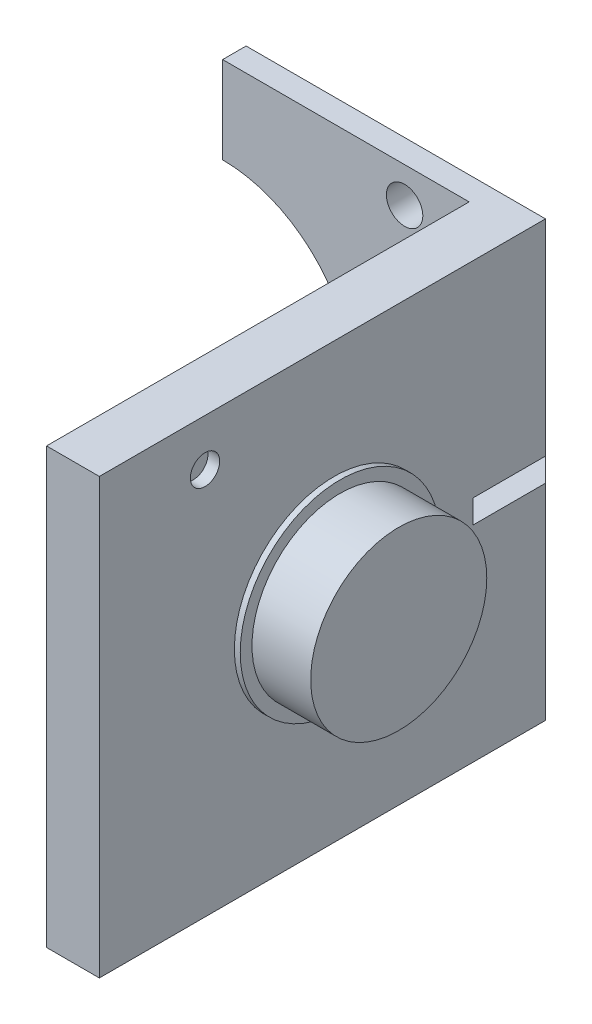
SolidWorks part; units mm, degrees
note: '?' marks a value the reader was unsure of.
ref_plane "Front Plane" through (0, 0, 0) normal (0, 0, 1) x (1, 0, 0)
ref_plane "Top Plane" through (0, 0, 0) normal (0, 1, 0) x (1, 0, 0)
ref_plane "Right Plane" through (0, 0, 0) normal (1, 0, 0) x (0, 0, -1)
sketch "Sketch1" plane through (0, 0, 0) normal (1, 0, 0) x (0, 0, -1)
  line L1 (0, 0) -> (30, 0)
  line L2 (0, 0) -> (0, 37)
  line L3 (0, 37) -> (30, 37)
  line L4 (30, 0) -> (30, 37)
  point P7 (30, 0)
  dimension "D1" = 37
  dimension "D2" = 30
extrude "Boss-Extrude1" add sketch "Sketch1" along normal blind 4.5
sketch "Sketch2" plane through (0, 0, 0) normal (-1, 0, 0) x (0, 0, 1)
  line L0 (0, 0) -> (-30, 0) construction
  line L9 (-30, 37) -> (-26, 37)
  line L10 (-30, 37) -> (-30, 0)
  line L11 (-30, 0) -> (-26, 0)
  line L12 (-26, 37) -> (-26, 0)
  dimension "D1" = 4
extrude "Boss-Extrude2" add sketch "Sketch2" along normal blind 42
sketch "Sketch3" plane through (-42, 0, 0) normal (-1, 0, 0) x (0, 0, 1)
  line L0 (-30, 37) -> (-30, 0)
  line L5 (-30, 0) -> (0, 0)
  line L6 (0, 0) -> (0, 37)
  line L7 (0, 37) -> (-30, 37)
  line L8 (-30, 37) -> (-30, 0) construction
extrude "Boss-Extrude3" add sketch "Sketch3" along normal blind 4.5
sketch "Sketch8" plane through (0, 0, -26) normal (0, 0, 1) x (1, 0, 0)
  line L0 (-42, 37) -> (0, 37) construction
  line L1 (0, 0) -> (0, 37) construction
  line L2 (-46.5, 37) -> (4.5, 0) construction
  circle A0 centre (-21, 18.5) radius 11.1
  point P5 (-21, 37)
  point P9 (0, 18.5)
  dimension "D1" = 22.2
extrude "Cut-Extrude1" cut sketch "Sketch8" against normal up to surface (4 mm away) up to face at (-21, 18.5, -30)
ref_axis "Axis1" through (-21, 18.5, -38.061) along (0, 0, 1)?
sketch "Sketch9" plane through (0, 0, -30) normal (0, 0, -1) x (-1, 0, 0)
  line L0 (5.5, 3) -> (36.5, 34) construction
  circle A0 centre (5.5, 34) radius 1.55
  circle A1 centre (36.5, 34) radius 1.55
  circle A2 centre (36.5, 3) radius 1.55
  circle A3 centre (5.5, 3) radius 1.55
  point P8 (21, 18.5)
  dimension "D4" = 3.1
  dimension "D2" = 31
  dimension "D3" = 31
extrude "Cut-Extrude2" cut sketch "Sketch9" against normal up to surface (4 mm away) up to face at (-9.9, 18.5, -26)
chamfer "Chamfer3" distance 2 angle 45 4 edges at (-21, 0, -30) (4.5, 18.5, -30) (-21, 37, -30) (-46.5, 18.5, -30)
sketch "草图6" plane through (4.5, 0, 0) normal (1, 0, 0) x (0, 0, -1)
  line L0 (38.061, 18.5) -> (-2.722, 18.5) construction
  circle A0 centre (10, 18.5) radius 7.5
  dimension "D1" = 15
extrude "凸台-拉伸2" add sketch "草图6" along normal blind 5.5
sketch "草图3" plane through (0, 37, 0) normal (0, 1, 0) x (1, 0, 0)
  circle A0 centre (4.5, 10) radius 1
sketch "草图5" plane through (-46.5, 0, 0) normal (-1, 0, 0) x (0, 0, 1)
  line L4 (-5, 18.5) -> (-15, 18.5) construction
  line L5 (-38.061, 18.5) -> (2.722, 18.5) construction
  circle A1 centre (-10, 18.5) radius 4
  point P8 (-10, 18.5)
  dimension "D1" = 8
extrude "凸台-拉伸1" add sketch "草图5" along normal blind 20.5
sketch "草图13" plane through (0, 0, 0) normal (-1, 0, 0) x (0, 0, 1)
  line L1 (-5, 22.5) -> (-5, 27)
  line L2 (-5, 27) -> (-15.5, 27)
  line L3 (-15.5, 27) -> (-15.5, 22.5)
  line L4 (-15.5, 22.5) -> (-5, 22.5)
  dimension "D1" = 4.5
sketch "草图15" plane through (-46.5, 0, 0) normal (-1, 0, 0) x (0, 0, 1)
  line L0 (-38.061, 18.5) -> (2.722, 18.5) construction
  circle A0 centre (-10, 18.5) radius 8.5
  dimension "D1" = 17
extrude "凸台-拉伸6" add sketch "草图15" along normal blind 0.5
sketch "草图16" plane through (4.5, 0, 0) normal (1, 0, 0) x (0, 0, -1)
  line L0 (38.061, 18.5) -> (-2.722, 18.5) construction
  circle A0 centre (10, 18.5) radius 8.5
  circle A1 centre (10, 18.5) radius 7.45
  dimension "D1" = 17
extrude "凸台-拉伸7" add sketch "草图16" along normal blind 0.5
sketch "草图17" plane through (0, 0, 0) normal (0, 0, 1) x (1, 0, 0)
  line L0 (0, 37) -> (4.5, 37)
  line L1 (4.5, 37) -> (4.5, 0)
  line L2 (4.5, 0) -> (0, 0)
  line L3 (0, 0) -> (0, 37)
extrude "凸台-拉伸8" add sketch "草图17" along normal blind 10
sketch "草图18" plane through (0, 37, 0) normal (0, 1, 0) x (1, 0, 0)
  line L0 (0, -8) -> (0, 2)
  line L1 (0, 26) -> (0, -10) construction
  line L2 (0, 2) -> (4.5, 2)
  line L3 (4.5, 28) -> (4.5, -10) construction
  line L4 (4.5, 2) -> (4.5, -8)
  line L5 (4.5, -8) -> (0, -8)
  line L6 (4.5, 28) -> (-46.5, 28) construction
  dimension "D1" = 10
  dimension "D2" = 26
sketch "草图23" plane through (4.5, 0, 0) normal (1, 0, 0) x (0, 0, -1)
  line L0 (-1, 42) -> (-1, 33) construction
  circle A0 centre (-1, 33) radius 1.25
  circle A1 centre (-1, 33) radius 1.25 construction
  dimension "D2" = 2.5
extrude "切除-拉伸4" cut sketch "草图23" against normal blind 1
ref_plane "基准面1" through (-21, 0, 0) normal (-1, 0, 0) x (0, 0, 1)
ref_axis "基准轴1" through (-67, 18.5, -10) along (1, 0, 0)?
sketch "草图26" plane through (-67, 0, 0) normal (-1, 0, 0) x (0, 0, 1)
  line L0 (-15, 18.5) -> (-5, 18.5) construction
  line L2 (-10, 23.5) -> (-10, 13.5) construction
  circle A0 centre (-10, 18.5) radius 5 construction
  arc A1 (-11.9365, 22) -> (-8.0635, 22) centre (-10, 21.5) cw
  arc A3 (-6.5, 20.4365) -> (-6.5, 16.5635) centre (-7, 18.5) cw
  circle A4 centre (-10, 18.5) radius 4 construction
  arc A5 (-11.9365, 15) -> (-8.0635, 15) centre (-10, 15.5) ccw
  arc A6 (-13.5, 16.5635) -> (-13.5, 20.4365) centre (-13, 18.5) cw
  circle A7 centre (-10, 18.5) radius 4
  point P5 (-10, 23.5)
  point P14 (-5, 18.5)
  point P20 (-10, 13.5)
  point P24 (-15, 18.5)
  dimension "D1" = 10
  dimension "D2" = 2
  dimension "D3" = 8
extrude "凸台-拉伸11" add sketch "草图26" against normal blind 20.5
sketch "草图25" plane through (-21, 0, 0) normal (-1, 0, 0) x (0, 0, 1)
  line L0 (21.5828, 37.676) -> (19.9289, -12.324)
  line L1 (19.9289, -12.324) -> (-38.5302, -10.3902)
  line L2 (-38.5302, -10.3902) -> (-38.5302, 37.676)
  line L3 (-38.5302, 37.676) -> (21.5828, 37.676)
  dimension "D1" = 50
extrude "切除-拉伸5" cut sketch "草图25" along normal through all
sketch "草图27" plane through (4.5, 0, 0) normal (1, 0, 0) x (0, 0, -1)
  line L0 (30, 35) -> (30, 2) construction
  line L1 (21.8401, 17.5) -> (30, 17.5)
  line L2 (21.8401, 17.5) -> (21.8401, 19.5)
  line L3 (21.8401, 19.5) -> (30, 19.5)
  line L4 (30, 17.5) -> (30, 19.5)
  line L5 (-10, 0) -> (28, 0) construction
  point P8 (21.8401, 17.5)
  dimension "D1" = 17.5
  dimension "D2" = 2
extrude "切除-拉伸6" cut sketch "草图27" against normal blind 2
